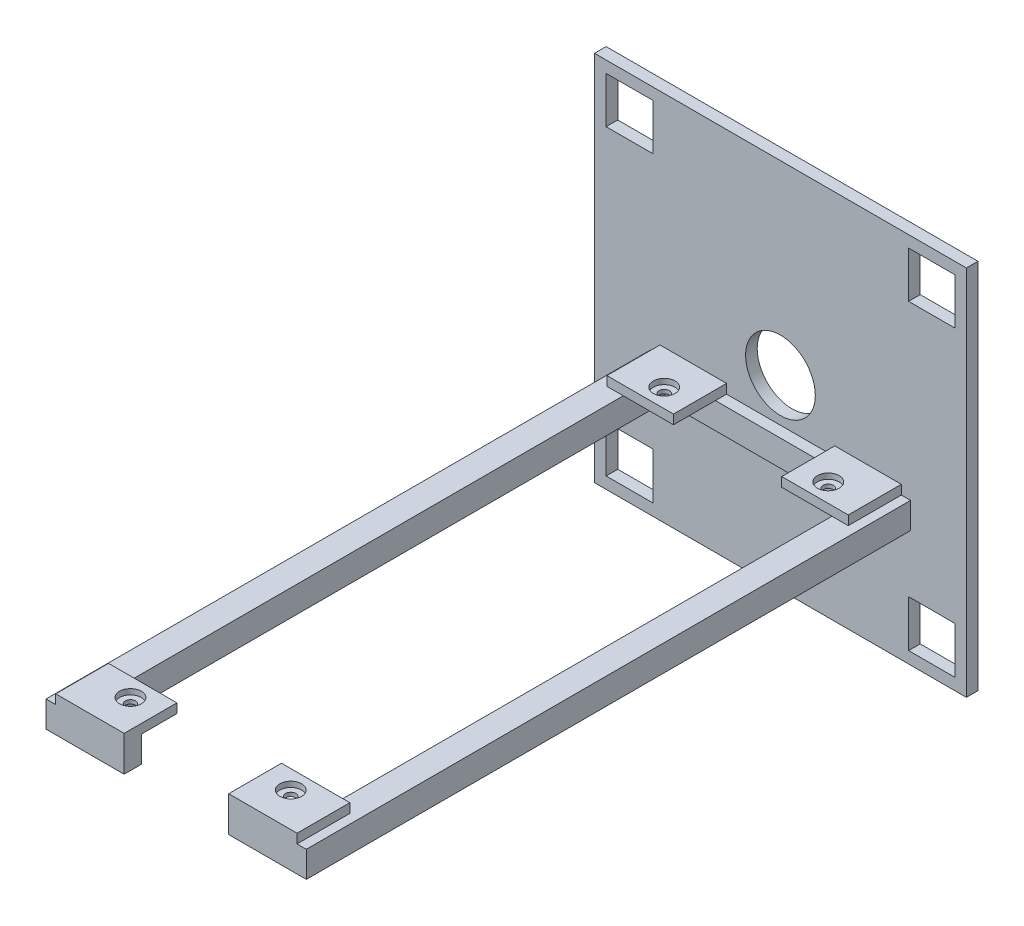
SolidWorks part; units mm, degrees
ref_plane "Front Plane" through (0, 0, 0) normal (0, 0, 1) x (1, 0, 0)
ref_plane "Top Plane" through (0, 0, 0) normal (0, 1, 0) x (1, 0, 0)
ref_plane "Right Plane" through (0, 0, 0) normal (1, 0, 0) x (0, 0, -1)
sketch "Sketch1" plane through (0, 0, 0) normal (0, 0, 1) x (1, 0, 0)
  line L1 (103.2829, -37.7023) -> (1.6829, -37.7023)
  line L2 (103.2829, -37.7023) -> (103.2829, 63.8977)
  line L3 (103.2829, 63.8977) -> (1.6829, 63.8977)
  line L4 (1.6829, -37.7023) -> (1.6829, 63.8977)
  dimension "D1" = 101.6
  dimension "D2" = 101.6
extrude "Boss-Extrude1" add sketch "Sketch1" along normal blind 3.175
sketch "Sketch2" plane through (0, 0, 3.175) normal (0, 0, 1) x (1, 0, 0)
  line L0 (16.9229, 63.8977) -> (16.9229, -37.7023) construction
  line L1 (103.2829, 63.8977) -> (1.6829, 63.8977) construction
  line L2 (1.6829, -37.7023) -> (103.2829, -37.7023) construction
  line L3 (88.0429, 63.8977) -> (88.0429, -37.7023) construction
  line L4 (1.6829, 24.9087) -> (103.2829, 24.9087) construction
  line L5 (1.6829, 63.8977) -> (1.6829, -37.7023) construction
  line L6 (103.2829, -37.7023) -> (103.2829, 63.8977) construction
  line L7 (1.6829, 1.2867) -> (103.2829, 1.2867) construction
  line L8 (1.6829, 13.0977) -> (103.2829, 13.0977) construction
  line L9 (16.9216, 1.2867) -> (16.9216, -5.8495)
  line L18 (16.9216, 1.2867) -> (24.0445, 1.2867)
  line L19 (24.0445, 1.2867) -> (24.0445, -5.8495)
  line L20 (16.9216, -5.8495) -> (24.0445, -5.8495)
  line L21 (88.043, -5.8495) -> (81.0521, -5.8495)
  line L22 (81.0521, 1.2867) -> (81.0521, -5.8495)
  line L23 (88.043, 1.2867) -> (81.0521, 1.2867)
  line L24 (88.043, 1.2867) -> (88.043, -5.8495)
  point P34 (0, 0)
  dimension "D1" = 15.24
  dimension "D2" = 15.24
  dimension "D3" = 50.8
  dimension "D4" = 11.811
  dimension "D5" = 11.811
  dimension "D6" = 0.0025
  dimension "D7" = 0.0003
extrude "Boss-Extrude2" add sketch "Sketch2" along normal blind 165.1
sketch "Sketch3" plane through (0, 0, 3.175) normal (0, 0, 1) x (1, 0, 0)
  line L5 (24.0445, 1.2867) -> (81.0521, 1.2867)
  line L6 (24.0445, 1.2867) -> (24.0445, -5.8495)
  line L7 (24.0445, -5.8495) -> (81.0521, -5.8495)
  line L8 (81.0521, 1.2867) -> (81.0521, -5.8495)
extrude "Boss-Extrude3" add sketch "Sketch3" along normal blind 3.048
sketch "Sketch6" plane through (81.0521, 0, 0) normal (-1, 0, 0) x (0, 0, 1)
  line L0 (168.275, 1.2867) -> (6.223, 1.2867) construction
  line L1 (168.275, -5.8495) -> (163.4411, -5.8495)
  line L2 (168.275, -5.8495) -> (168.275, 1.2867)
  line L3 (168.275, 1.2867) -> (163.4411, 1.2867)
  line L4 (163.4411, -5.8495) -> (163.4411, 1.2867)
extrude "Boss-Extrude6" add sketch "Sketch6" along normal blind 14.224
sketch "Sketch7" plane through (24.0445, 0, 0) normal (1, 0, 0) x (0, 0, -1)
  line L0 (-168.275, -5.8495) -> (-6.223, -5.8495) construction
  line L1 (-168.275, 1.2867) -> (-163.5304, 1.2867)
  line L2 (-168.275, 1.2867) -> (-168.275, -5.8495)
  line L3 (-168.275, -5.8495) -> (-163.5304, -5.8495)
  line L4 (-163.5304, 1.2867) -> (-163.5304, -5.8495)
extrude "Boss-Extrude7" add sketch "Sketch7" along normal blind 14.224
sketch "Sketch12" plane through (0, 1.2867, 0) normal (0, 1, 0) x (1, 0, 0)
  line L0 (88.043, -3.175) -> (16.9216, -3.175) construction
  line L1 (66.8281, -168.275) -> (85.5119, -168.275)
  line L2 (66.8281, -168.275) -> (66.8281, -153.8458)
  line L3 (66.8281, -153.8458) -> (85.5119, -153.8458)
  line L4 (85.5119, -168.275) -> (85.5119, -153.8458)
  line L5 (38.2685, -168.275) -> (19.5679, -168.275)
  line L6 (38.2685, -168.275) -> (38.2685, -153.8458)
  line L7 (38.2685, -153.8458) -> (19.5679, -153.8458)
  line L8 (19.5679, -168.275) -> (19.5679, -153.8458)
  line L9 (19.5679, -3.175) -> (37.7618, -3.175)
  line L10 (19.5679, -3.175) -> (19.5679, -17.6724)
  line L11 (19.5679, -17.6724) -> (37.7618, -17.6724)
  line L12 (37.7618, -3.175) -> (37.7618, -17.6724)
  line L14 (85.5119, -3.175) -> (67.3359, -3.175)
  line L15 (85.5119, -3.175) -> (85.5119, -17.6724)
  line L16 (85.5119, -17.6724) -> (67.3359, -17.6724)
  line L17 (67.3359, -3.175) -> (67.3359, -17.6724)
extrude "Boss-Extrude10" add sketch "Sketch12" along normal blind 2.54
hole_wizard "CBORE for #3 Binding Head Machine Screw2" positions "Sketch15" profile "Sketch16" counterbore size "#3" standard "ANSI Inch" end condition through all
sketch "Sketch15" plane through (0, 3.8267, 0) normal (0, 1, 0) x (1, 0, 0)
  line L0 (38.2685, -168.275) -> (38.2685, -153.8458) construction
  line L1 (38.2685, -153.8458) -> (19.5679, -153.8458) construction
  line L2 (66.8281, -153.8458) -> (66.8281, -168.275) construction
  line L4 (19.5679, -17.6724) -> (37.7618, -17.6724) construction
  point P0 (30.6485, -158.9258)
  point P7 (74.4481, -158.9258)
  point P9 (30.1418, -12.5924)
  point P18 (74.9559, -12.5924)
  dimension "D1" = 7.62
  dimension "D2" = 5.08
  dimension "D3" = 7.62
  dimension "D4" = 5.08
sketch "Sketch16" plane through (30.6485, 3.8267, 158.9258) normal (1, 0, 0) x (0, 0, 1)
  line L0 (0, 0) -> (0, 41.529)
  line L1 (0, 41.529) -> (1.397, 41.529)
  line L3 (1.397, 41.529) -> (1.397, 1.4986)
  line L4 (1.397, 1.4986) -> (2.9769, 1.4986)
  line L5 (2.9769, 1.4986) -> (2.9769, 0)
  line L7 (2.9769, 0) -> (0, 0)
  line L11 (0, -6.35) -> (0, 107.95) construction
  dimension "Thru Hole Dia." = 2.794
  dimension "Thru Hole Depth" = 41.529
  dimension "C'Bore Dia." = 5.9538
  dimension "C'Bore Depth" = 1.4986
sketch "Sketch19" plane through (0, 0, 3.175) normal (0, 0, 1) x (1, 0, 0)
  line L0 (103.2829, 63.8977) -> (1.6829, 63.8977) construction
  line L1 (4.8579, 60.7227) -> (17.6171, 60.7227)
  line L2 (4.8579, 60.7227) -> (4.8579, 48.1127)
  line L3 (4.8579, 48.1127) -> (17.6171, 48.1127)
  line L4 (17.6171, 60.7227) -> (17.6171, 48.1127)
  line L5 (1.6829, 63.8977) -> (1.6829, -37.7023) construction
  line L6 (103.2829, -37.7023) -> (103.2829, 63.8977) construction
  line L7 (100.1079, -34.5273) -> (87.4979, -34.5273)
  line L8 (100.1079, -34.5273) -> (100.1079, -21.7681)
  line L9 (100.1079, -21.7681) -> (87.4979, -21.7681)
  line L10 (87.4979, -34.5273) -> (87.4979, -21.7681)
  line L11 (1.6829, -37.7023) -> (103.2829, -37.7023) construction
  line L13 (100.1079, 60.7227) -> (87.4979, 60.7227)
  line L14 (100.1079, 60.7227) -> (100.1079, 48.1127)
  line L15 (100.1079, 48.1127) -> (87.4979, 48.1127)
  line L16 (87.4979, 60.7227) -> (87.4979, 48.1127)
  line L17 (4.8579, -34.5273) -> (17.6171, -34.5273)
  line L18 (4.8579, -34.5273) -> (4.8579, -21.7681)
  line L19 (4.8579, -21.7681) -> (17.6171, -21.7681)
  line L20 (17.6171, -34.5273) -> (17.6171, -21.7681)
  dimension "D1" = 3.175
  dimension "D2" = 3.175
  dimension "D3" = 3.175
  dimension "D4" = 3.175
extrude "Cut-Extrude1" cut sketch "Sketch19" against normal blind 3.175
sketch "Sketch20" plane through (0, 0, 0) normal (0, 0, -1) x (-1, 0, 0)
  line L0 (-103.2829, 13.0977) -> (-1.6829, 13.0977) construction
  line L1 (-103.2829, -37.7023) -> (-103.2829, 63.8977) construction
  line L2 (-1.6829, 63.8977) -> (-1.6829, -37.7023) construction
sketch "Sketch24" plane through (38.2685, 0, 0) normal (1, 0, 0) x (0, 0, -1)
  line L1 (-168.275, -5.8495) -> (-163.5304, -5.8495)
  line L2 (-168.275, -5.8495) -> (-168.275, 1.2867)
  line L3 (-168.275, 1.2867) -> (-163.5304, 1.2867)
  line L4 (-163.5304, -5.8495) -> (-163.5304, 1.2867)
hole_wizard "3/4 (0.75) Diameter Hole1" positions "Sketch26" profile "Sketch27" hole size "3/4" standard "ANSI Inch" end condition through all
sketch "Sketch26" plane through (0, 0, 0) normal (0, 0, -1) x (-1, 0, 0)
  line L0 (-103.2829, 13.0977) -> (-1.6829, 13.0977) construction
  point P0 (-52.4829, 13.0977)
sketch "Sketch27" plane through (52.4829, 13.0977, 0) normal (1, 0, 0) x (0, 1, 0)
  line L0 (0, 0) -> (0, 168.275)
  line L1 (0, 168.275) -> (9.525, 168.275)
  line L2 (9.525, 168.275) -> (9.525, 0)
  line L5 (9.525, 0) -> (0, 0)
  line L11 (0, -6.35) -> (0, 107.95) construction
  dimension "Thru Hole Dia." = 19.05
  dimension "Thru Hole Depth" = 168.275
